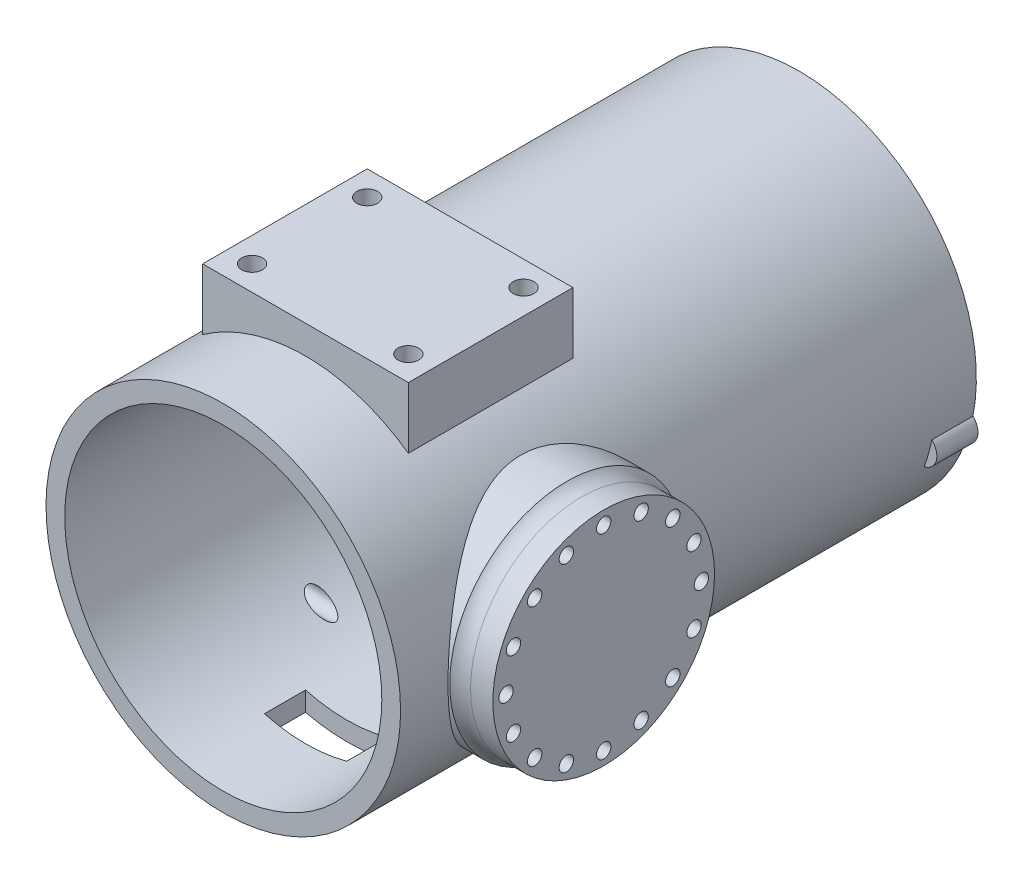
SolidWorks part; units mm, degrees
other "Markup1"
sketch "Sketch14" plane through (-43.1, 43.1, 140) normal (-0.1765, 0.0048, 0.9843) x (0.9842, -0.0149, 0.1765)
other "Markup2"
sketch "Sketch23" plane through (45.1, -43.1, 140) normal (0.9491, -0.0629, 0.3087) x (0.311, 0.031, -0.9499)
ref_plane "Front Plane" through (0, 0, 0) normal (0, 0, 1) x (1, 0, 0)
ref_plane "Top Plane" through (0, 0, 0) normal (0, 1, 0) x (1, 0, 0)
ref_plane "Right Plane" through (0, 0, 0) normal (1, 0, 0) x (0, 0, -1)
sketch "Sketch1" plane through (0, 0, 0) normal (0, 0, 1) x (1, 0, 0)
  circle A1 centre (0, 0) radius 43.1
  dimension "D1" = 86.2
extrude "Main Body" add sketch "Sketch1" along normal blind 140
ref_plane "Plane1" through (0, 43.1, 0) normal (0, 1, 0) x (1, 0, 0)
sketch "Sketch34" [suppressed] plane through (0, 43.1, 0) normal (0, 1, 0) x (1, 0, 0)
  line L6 (-5, -13) -> (5, -13)
  line L8 (-5, -13) -> (-5, -3)
  line L9 (-5, -3) -> (5, -3)
  line L10 (5, -13) -> (5, -3)
  line L11 (-5, -13) -> (5, -3) construction
  line L12 (-5, -3) -> (5, -13) construction
  point P0 (0, -8)
  dimension "D1" = 8
  dimension "D2" = 10
  dimension "D3" = 10
sketch "Sketch6" plane through (0, 43.1, 0) normal (0, 1, 0) x (1, 0, 0)
  line L2 (-5, -47.7) -> (5, -47.7)
  line L3 (-5, -47.7) -> (-5, -37.7)
  line L4 (-5, -37.7) -> (5, -37.7)
  line L5 (5, -47.7) -> (5, -37.7)
  line L6 (-5, -47.7) -> (5, -37.7) construction
  line L7 (-5, -37.7) -> (5, -47.7) construction
  point P2 (0, -42.7)
  dimension "D2" = 10
  dimension "D1" = 42.7
  dimension "D3" = 10
extrude "Cut-Extrude3" cut sketch "Sketch6" against normal through all
pattern_circular "Rotated Plug Pattern" count 2 every 90 about axis through (0, 0, 140) along (0, 0, 1) of "Cut-Extrude3"
ref_plane "Plane2" through (52.5, 0, 0) normal (1, 0, 0) x (0, 0, -1)
sketch "Sketch8" plane through (52.5, 0, 0) normal (1, 0, 0) x (0, 0, -1)
  circle A0 centre (-100, 0) radius 26.95
  dimension "D1" = 53.9
  dimension "D2" = 100
extrude "Boss-Extrude2" add sketch "Sketch8" against normal blind 20
mirror "Mirror1" [suppressed] about plane through (0, 0, 0) normal (1, 0, 0)
ref_plane "Plane3" through (0, 50, 0) normal (0, 1, 0) x (1, 0, 0)
sketch "Sketch33" plane through (0, 50, 0) normal (0, 1, 0) x (1, 0, 0)
  line L1 (-25, -120) -> (25, -120)
  line L2 (-25, -120) -> (-25, -80)
  line L3 (-25, -80) -> (25, -80)
  line L4 (25, -120) -> (25, -80)
  line L5 (-25, -120) -> (25, -80) construction
  line L6 (-25, -80) -> (25, -120) construction
  point P0 (0, -100)
  dimension "D1" = 100
  dimension "D2" = 40
  dimension "D3" = 50
extrude "Boss-Extrude11" add sketch "Sketch33" against normal blind 22
sketch "Sketch35" plane through (0, 50, 0) normal (0, 1, 0) x (1, 0, 0)
  line L0 (-25, -120) -> (-25, -80) construction
  line L1 (25, -120) -> (25, -80) construction
  line L2 (25, -80) -> (-25, -80) construction
  line L3 (-25, -120) -> (25, -120) construction
  circle A0 centre (-19, -86) radius 2.525
  circle A1 centre (19, -86) radius 2.525
  circle A2 centre (-19, -114) radius 2.525
  circle A3 centre (19, -114) radius 2.525
  dimension "D1" = 5.05
  dimension "D2" = 6
  dimension "D3" = 6
  dimension "D4" = 6
  dimension "D5" = 6
extrude "Cut-Extrude14" cut sketch "Sketch35" against normal blind 4
sketch "Sketch5" plane through (0, 0, 140) normal (0, 0, 1) x (1, 0, 0)
  circle A0 centre (0, 0) radius 32
  dimension "D1" = 64
extrude "Hole 1" cut sketch "Sketch5" against normal through all
sketch "Sketch10" plane through (0, 0, 0) normal (0, 1, 0) x (1, 0, 0)
  line L0 (43.1, 0) -> (-43.1, 0) construction
  line L1 (-10, -120) -> (10, -120)
  line L2 (-10, -120) -> (-10, -110)
  line L3 (-10, -110) -> (10, -110)
  line L4 (10, -120) -> (10, -110)
  line L5 (-10, -120) -> (10, -110) construction
  line L6 (-10, -110) -> (10, -120) construction
  point P0 (0, -115)
  point P7 (-10, -115)
  dimension "D1" = 110
  dimension "D2" = 10
  dimension "D3" = 20
extrude "Motor Wire Hole" cut sketch "Sketch10" against normal through all
sketch "Sketch27" plane through (0, 0, 0) normal (1, 0, 0) x (0, 0, -1)
  line L1 (-100, -36.5) -> (-60, -36.5)
  line L2 (-100, -36.5) -> (-100, -27.5)
  line L3 (-100, -27.5) -> (-60, -27.5)
  line L4 (-60, -36.5) -> (-60, -27.5)
  dimension "D1" = 60
  dimension "D2" = 27.5
  dimension "D3" = 40
  dimension "D4" = 9
extrude "Boss-Extrude9" add sketch "Sketch27" along normal blind 33 and the other way blind 33
sketch "Sketch11" plane through (0, 0, 0) normal (1, 0, 0) x (0, 0, -1)
  circle A0 centre (-65, -32) radius 2.25
  circle A1 centre (-95, -32) radius 2.25
  dimension "D3" = 4.5
  dimension "D1" = 65
  dimension "D2" = 32
  dimension "D4" = 30
extrude "Cut-Extrude6" cut sketch "Sketch11" against normal through all both and the other way through all
sketch "Sketch28" plane through (-33, 0, 0) normal (-1, 0, 0) x (0, 0, 1)
  line L0 (62.8927, -28.35) -> (67.1073, -28.35)
  line L1 (67.1073, -28.35) -> (69.2147, -32)
  line L2 (69.2147, -32) -> (67.1073, -35.65)
  line L3 (67.1073, -35.65) -> (62.8927, -35.65)
  line L4 (62.8927, -35.65) -> (60.7853, -32)
  line L6 (60.7853, -32) -> (62.8927, -28.35)
  line L7 (92.8927, -28.35) -> (97.1073, -28.35)
  line L8 (97.1073, -28.35) -> (99.2147, -32)
  line L9 (99.2147, -32) -> (97.1073, -35.65)
  line L10 (97.1073, -35.65) -> (92.8927, -35.65)
  line L11 (92.8927, -35.65) -> (90.7853, -32)
  line L12 (90.7853, -32) -> (92.8927, -28.35)
  circle A0 centre (65, -32) radius 3.65 construction
  circle A1 centre (65, -32) radius 2.25 construction
  circle A2 centre (95, -32) radius 3.65 construction
  circle A3 centre (95, -32) radius 2.25 construction
  dimension "D2" = 7.3
extrude "Cut-Extrude7" cut sketch "Sketch28" against normal blind 3
sketch "Sketch29" plane through (33, 0, 0) normal (1, 0, 0) x (0, 0, -1)
  circle A0 centre (-95, -32) radius 3.6
  circle A1 centre (-65, -32) radius 3.6
  dimension "D1" = 7.2
extrude "Cut-Extrude8" cut sketch "Sketch29" against normal blind 4
sketch "Sketch2" plane through (0, 0, 140) normal (0, 0, 1) x (1, 0, 0)
  circle A0 centre (0, 0) radius 38.55
  dimension "D1" = 77.1
extrude "Cut-Extrude5" cut sketch "Sketch2" against normal blind 135
sketch "Sketch9" plane through (0, 0, 5) normal (0, 0, 1) x (1, 0, 0)
  circle A0 centre (0, 0) radius 38.55
  circle A1 centre (0, 0) radius 36.89
  circle A2 centre (0, 0) radius 38.55 construction
  dimension "D2" = 1.66
extrude "Boss-Extrude3" add sketch "Sketch9" along normal blind 10
extrude "Cut-Extrude13" [suppressed] cut sketch "Sketch34" against normal blind 15
sketch "Sketch30" plane through (52.5, 0, 0) normal (1, 0, 0) x (0, 0, -1)
  line L0 (-100, 23.75) -> (-100, 0) construction
  circle A0 centre (-100, 0) radius 23.75 construction
  circle A1 centre (-100, 23.75) radius 1.75
  circle A2 centre (-90.9113, 21.9421) radius 1.75
  circle A3 centre (-83.2062, 16.7938) radius 1.75
  circle A4 centre (-78.0579, 9.0887) radius 1.75
  circle A5 centre (-76.25, 0) radius 1.75
  circle A6 centre (-78.0579, -9.0887) radius 1.75
  circle A7 centre (-83.2062, -16.7938) radius 1.75
  circle A8 centre (-90.9113, -21.9421) radius 1.75
  circle A9 centre (-100, -23.75) radius 1.75
  circle A10 centre (-109.0887, -21.9421) radius 1.75
  circle A11 centre (-116.7938, -16.7938) radius 1.75
  circle A12 centre (-121.9421, -9.0887) radius 1.75
  circle A13 centre (-123.75, 0) radius 1.75
  circle A14 centre (-121.9421, 9.0887) radius 1.75
  circle A15 centre (-116.7938, 16.7938) radius 1.75
  circle A16 centre (-109.0887, 21.9421) radius 1.75
  point P38 (-100, 0)
  dimension "D1" = 47.5
  dimension "D2" = 3.5
  dimension "D3" = 16
extrude "Cut-Extrude9" cut sketch "Sketch30" against normal up to surface (22.1349 mm away) up to face at (38.55, 0, 15)
sketch "Sketch31" plane through (52.5, 0, 0) normal (1, 0, 0) x (0, 0, -1)
  line L0 (0, -43.1) -> (0, 43.1) construction
  line L1 (0, -15) -> (-10, -15)
  line L2 (0, -15) -> (0, -7.5)
  line L3 (0, -7.5) -> (-10, -7.5)
  line L4 (-10, -15) -> (-10, -7.5)
  dimension "D1" = 15
  dimension "D2" = 7.5
  dimension "D3" = 10
extrude "Boss-Extrude10" add sketch "Sketch31" against normal up to body from offset 9 offset against normal yes
sketch "Sketch32" plane through (0, 0, 0) normal (0, 0, -1) x (-1, 0, 0)
  line L0 (-43.5, -11.25) -> (-29.9573, -11.25) construction
  line L1 (-43.5, -15) -> (-43.5, -7.5) construction
  line L3 (-42.4424, -7.5) -> (-43.5, -7.5) construction
  line L5 (-43.5, -15) -> (-43.5, -7.5)
  line L6 (-43.5, -7.5) -> (-42.4424, -7.5)
  circle A0 centre (0, 0) radius 32 construction
  arc A2 (-40.4056, -15) -> (-42.4424, -7.5) centre (0, 0) ccw construction
  arc A3 (-40.4056, -15) -> (-42.2658, -8.4385) centre (-39.6806, -11.25) cw
  arc A4 (-42.2658, -8.4385) -> (-42.4424, -7.5) centre (0, 0) cw
  line M3 (-42.4424, -7.5) -> (-43.5, -7.5)
  line M4 (-43.5, -7.5) -> (-43.5, -15)
  line M5 (-43.5, -15) -> (-40.4056, -15)
extrude "Cut-Extrude10" cut sketch "Sketch32" against normal up to surface (10 mm away) contours M4 M3 | L5 M5 region at (43.0347, -8.5479, 0) region at (42.7123, -14.1508, 0) up to face at (42.5043, -11.2615, 10)
ref_plane "Plane4" through (-43.1, 0, 0) normal (-1, 0, 0) x (0, 0, 1)
sketch "Sketch36" plane through (-43.1, 0, 0) normal (-1, 0, 0) x (0, 0, 1)
  line L0 (140, -43.1) -> (140, 43.1) construction
  line L1 (52.58, 43.1) -> (-52.58, 43.1) construction
  circle A0 centre (110, 8.1) radius 19.05
  dimension "D1" = 38.1
  dimension "D2" = 30
  dimension "D3" = 35
extrude "Cut-Extrude15" [suppressed] cut sketch "Sketch36" against normal up to next
sketch "Sketch37" plane through (52.5, 0, 0) normal (1, 0, 0) x (0, 0, -1)
  circle A0 centre (-100, 23.75) radius 1.75 construction
  circle A1 centre (-90.9113, 21.9421) radius 1.75 construction
  circle A2 centre (-83.2062, 16.7938) radius 1.75 construction
  circle A3 centre (-78.0579, 9.0887) radius 1.75 construction
  circle A4 centre (-76.25, 0) radius 1.75 construction
  circle A5 centre (-78.0579, -9.0887) radius 1.75 construction
  circle A6 centre (-83.2062, -16.7938) radius 1.75 construction
  circle A7 centre (-90.9113, -21.9421) radius 1.75 construction
  circle A8 centre (-100, -23.75) radius 1.75 construction
  circle A9 centre (-109.0887, -21.9421) radius 1.75 construction
  circle A10 centre (-116.7938, -16.7938) radius 1.75 construction
  circle A11 centre (-121.9421, -9.0887) radius 1.75 construction
  circle A12 centre (-123.75, 0) radius 1.75 construction
  circle A13 centre (-121.9421, 9.0887) radius 1.75 construction
  circle A14 centre (-116.7938, 16.7938) radius 1.75 construction
  circle A15 centre (-109.0887, 21.9421) radius 1.75 construction
  circle A16 centre (-100, 23.75) radius 1.75
  circle A17 centre (-90.9113, 21.9421) radius 1.75
  circle A18 centre (-83.2062, 16.7938) radius 1.75
  circle A19 centre (-78.0579, 9.0887) radius 1.75
  circle A20 centre (-76.25, 0) radius 1.75
  circle A21 centre (-78.0579, -9.0887) radius 1.75
  circle A22 centre (-83.2062, -16.7938) radius 1.75
  circle A23 centre (-90.9113, -21.9421) radius 1.75
  circle A24 centre (-100, -23.75) radius 1.75
  circle A25 centre (-109.0887, -21.9421) radius 1.75
  circle A26 centre (-116.7938, -16.7938) radius 1.75
  circle A27 centre (-121.9421, -9.0887) radius 1.75
  circle A28 centre (-123.75, 0) radius 1.75
  circle A29 centre (-121.9421, 9.0887) radius 1.75
  circle A30 centre (-116.7938, 16.7938) radius 1.75
  circle A31 centre (-109.0887, 21.9421) radius 1.75
  circle A32 centre (-100, 23.75) radius 3.75
  circle A33 centre (-90.9113, 21.9421) radius 3.75
  circle A34 centre (-83.2062, 16.7938) radius 3.75
  circle A35 centre (-78.0579, 9.0887) radius 3.75
  circle A36 centre (-76.25, 0) radius 3.75
  circle A37 centre (-78.0579, -9.0887) radius 3.75
  circle A38 centre (-83.2062, -16.7938) radius 3.75
  circle A39 centre (-90.9113, -21.9421) radius 3.75
  circle A40 centre (-100, -23.75) radius 3.75
  circle A41 centre (-109.0887, -21.9421) radius 3.75
  circle A42 centre (-116.7938, -16.7938) radius 3.75
  circle A43 centre (-121.9421, -9.0887) radius 3.75
  circle A44 centre (-123.75, 0) radius 3.75
  circle A45 centre (-121.9421, 9.0887) radius 3.75
  circle A46 centre (-116.7938, 16.7938) radius 3.75
  circle A47 centre (-109.0887, 21.9421) radius 3.75
  circle M1 centre (-109.0887, 21.9421) radius 1.75
  circle M2 centre (-116.7938, 16.7938) radius 1.75
  circle M3 centre (-121.9421, 9.0887) radius 1.75
  circle M4 centre (-123.75, 0) radius 1.75
  circle M5 centre (-121.9421, -9.0887) radius 1.75
  circle M6 centre (-116.7938, -16.7938) radius 1.75
  circle M7 centre (-109.0887, -21.9421) radius 1.75
  circle M8 centre (-100, -23.75) radius 1.75
  circle M9 centre (-90.9113, -21.9421) radius 1.75
  circle M10 centre (-83.2062, -16.7938) radius 1.75
  circle M11 centre (-78.0579, -9.0887) radius 1.75
  circle M12 centre (-76.25, 0) radius 1.75
  circle M13 centre (-78.0579, 9.0887) radius 1.75
  circle M14 centre (-83.2062, 16.7938) radius 1.75
  circle M15 centre (-90.9113, 21.9421) radius 1.75
  circle M16 centre (-100, 23.75) radius 1.75
  circle M17 centre (-100, 0) radius 26.95
  dimension "D1" = 2
extrude "Boss-Extrude13" add sketch "Sketch37" against normal blind 5 from offset 18 contours A47 M17 M1 | A47 M17 | A32 M17 M16 | A32 M17 | A33 M17 M15 | A33 M17 | A40 M17 M8 | A40 M17 | A39 M17 M9 | A39 M17 | A41 M17 | A41 M17 M7 region at (52.5, 20.5336, 101.7207) region at (52.5, 27.1554, 100) region at (52.5, 24.801, 89.7271) region at (52.5, 25.0884, 89.6081) region at (52.5, 25.0884, 110.3919) region at (52.5, 24.2552, 106.2724) region at (52.5, -24.801, 89.7271) region at (52.5, -25.0884, 89.6081) region at (52.5, -25.0884, 110.3919) region at (52.5, -18.455, 110.1479) region at (52.5, -26.8477, 100) region at (52.5, -27.1554, 100) offset against normal yes
extrude "Cut-Extrude17" cut sketch "Sketch37<6>" along normal blind 9 from offset 30 contours A47 M17 M1 | M1 | A47 M17 | A32 | A33 | A41 | A40 | A39 region at (52.5, 21.9421, 109.0887) region at (52.5, 25.0884, 110.3919) region at (52.5, 24.2552, 106.2724) offset against normal yes
sketch "Sketch37<6>" plane through (52.5, 0, 0) normal (1, 0, 0) x (0, 0, -1) same geometry as "Sketch37"
extrude "Boss-Extrude14" add sketch "Sketch37<7>" against normal blind 10 from offset 10 contours A42 M17 M6 | A42 M17 | A38 M17 M10 | A38 M17 | A46 M17 M2 | A46 M17 | A34 M17 M14 | A34 M17 region at (52.5, 18.9815, 81.0185) region at (52.5, 19.2018, 80.7982) region at (52.5, 19.2018, 119.2018) region at (52.5, 19.6114, 114.4831) region at (52.5, -18.9815, 81.0185) region at (52.5, -19.2018, 80.7982) region at (52.5, -19.2018, 119.2018) region at (52.5, -13.1675, 117.1523) offset against normal yes
sketch "Sketch37<7>" plane through (52.5, 0, 0) normal (1, 0, 0) x (0, 0, -1) same geometry as "Sketch37"
extrude "Cut-Extrude18" cut sketch "Sketch37<8>" along normal blind 13 from offset 30 contours A42 | A38 | A34 | A46 offset against normal yes
sketch "Sketch37<8>" plane through (52.5, 0, 0) normal (1, 0, 0) x (0, 0, -1) same geometry as "Sketch37"
extrude "Boss-Extrude16" add sketch "Sketch37<10>" against normal blind 6 from offset 10 contours A44 M17 M4 | A44 M17 | A43 M17 M5 | A43 M17 | A45 M17 M3 | A45 M17 | A36 M17 M12 | A36 M17 | A35 M17 M13 | A35 M17 | A37 M17 M11 | A37 M17 region at (52.5, 10.2729, 75.199) region at (52.5, 10.3919, 74.9116) region at (52.5, 10.3919, 125.0884) region at (52.5, 12.3035, 120.2253) region at (52.5, 1.0374, 73.1723) region at (52.5, 0, 72.8446) region at (52.5, 0, 127.1554) region at (52.5, 3.4911, 122.6924) region at (52.5, -10.2729, 75.199) region at (52.5, -10.3919, 74.9116) region at (52.5, -10.3919, 125.0884) region at (52.5, -5.4617, 121.5862) offset against normal yes
sketch "Sketch37<10>" plane through (52.5, 0, 0) normal (1, 0, 0) x (0, 0, -1) same geometry as "Sketch37"
extrude "Cut-Extrude19" cut sketch "Sketch37<9>" along normal blind 5.5 from offset 20 contours A44 M17 M4 | A36 M17 M12 | M12 | M4 | A44 M17 | A36 M17 | A43 | A45 | A35 | A37 region at (52.5, 0, 76.25) region at (52.5, 0, 123.75) region at (52.5, 1.0374, 73.1723) region at (52.5, 0, 72.8446) region at (52.5, 0, 127.1554) region at (52.5, 3.4911, 122.6924) offset against normal yes
sketch "Sketch37<9>" plane through (52.5, 0, 0) normal (1, 0, 0) x (0, 0, -1) same geometry as "Sketch37"
sketch "Sketch38" plane through (52.5, 0, 0) normal (1, 0, 0) x (0, 0, -1)
  circle A0 centre (-100, 0) radius 26.95 construction
  circle A1 centre (-100, 0) radius 26.95
  circle A2 centre (-100, 0) radius 28.45
  circle M17 centre (-100, 0) radius 26.95
  dimension "D1" = 1.5
extrude "Boss-Extrude15" add sketch "Sketch38" against normal up to next from offset 9 contours M17 | M17 | M17 | M17 region at (52.5, 0, 127.6453) offset against normal yes
fillet "Fillet1" radius 5 1 edges at (43.5, 0, 73.05)
sketch "Sketch40" plane through (0, 0, 37.7) normal (0, 0, 1) x (1, 0, 0)
  circle A0 centre (0, 0) radius 36.89 construction
  circle A1 centre (0, 0) radius 36.89
  circle A2 centre (0, 0) radius 43.1 construction
  circle A3 centre (0, 0) radius 43.1
extrude "Boss-Extrude17" add sketch "Sketch40" along normal blind 10
extrude "Boss-Extrude18" add sketch "Sketch40<2>" against normal blind 10 from offset 6.35 offset against normal yes
sketch "Sketch40<2>" plane through (0, 0, 37.7) normal (0, 0, 1) x (1, 0, 0) same geometry as "Sketch40"
